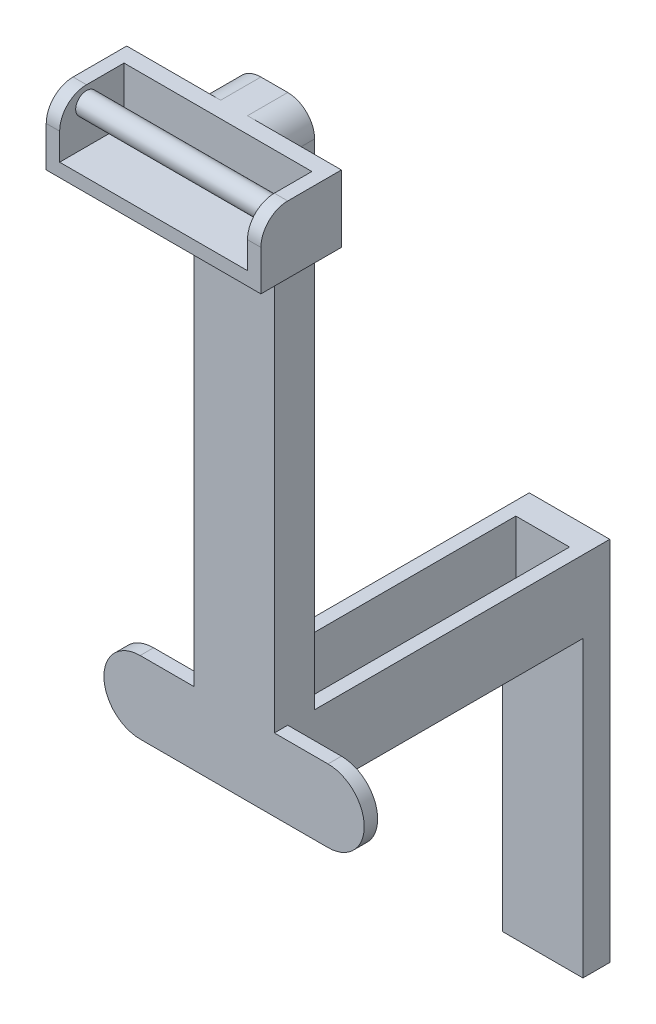
SolidWorks part; units mm, degrees
ref_plane "Front Plane" through (0, 0, 0) normal (0, 0, 1) x (1, 0, 0)
ref_plane "Top Plane" through (0, 0, 0) normal (0, 1, 0) x (1, 0, 0)
ref_plane "Right Plane" through (0, 0, 0) normal (1, 0, 0) x (0, 0, -1)
sketch "Sketch1" plane through (0, 0, 0) normal (0, 0, 1) x (1, 0, 0)
  line L0 (50, 212.065) -> (-20, 212.065) construction
  line L1 (30, -62.835) -> (0, -62.835)
  line L2 (30, -62.835) -> (30, 419.765)
  line L3 (30, 419.765) -> (0, 419.765)
  line L4 (0, -62.835) -> (0, 419.765)
  line L5 (30, -62.835) -> (0, 419.765) construction
  line L6 (30, 419.765) -> (0, -62.835) construction
  line L7 (50, 198.565) -> (-20, 198.565)
  line L8 (50, 225.565) -> (-20, 225.565)
  arc A0 (50, 198.565) -> (50, 225.565) centre (50, 212.065) ccw
  arc A1 (-20, 225.565) -> (-20, 198.565) centre (-20, 212.065) ccw
  point P0 (15, 178.465)
  point P7 (15, 212.065)
  dimension "D1" = 482.6
  dimension "D2" = 27
  dimension "D3" = 30
  dimension "D4" = 33.6
  dimension "D5" = 70
  dimension "D6" = 0
extrude "Extrude1" add sketch "Sketch1" along normal blind 15 contours L8 L2 L3 L4 | L7 A0 L8 L2 | L2 L8 L4 L7 | L8 A1 L7 L4 | L2 L7 L4 L1 region at (15, 67.865, 0) region at (15, 212.065, 0) region at (45.4498, 212.065, 0) region at (-15.4498, 212.065, 0) region at (15, 322.665, 0)
fillet "Fillet1" radius 10 4 edges at (30, -62.835, 7.5) (0, -62.835, 7.5) (0, 419.765, 7.5) (30, 419.765, 7.5)
sketch "Sketch2" plane through (0, 0, 0) normal (0, 0, -1) x (-1, 0, 0)
  line L0 (-50, 225.565) -> (-30, 225.565) construction
  line L1 (-50, 198.565) -> (-30, 198.565) construction
  line L2 (0, 198.565) -> (20, 198.565) construction
  line L3 (0, 225.565) -> (20, 225.565) construction
  line L4 (-50, 225.565) -> (-30, 225.565)
  line L5 (-50, 198.565) -> (-30, 198.565)
  line L6 (0, 198.565) -> (20, 198.565)
  line L7 (0, 225.565) -> (20, 225.565)
  line L8 (-30, 225.565) -> (-30, 198.565)
  line L9 (0, 225.565) -> (0, 198.565)
  arc A0 (20, 198.565) -> (20, 225.565) centre (20, 212.065) ccw construction
  arc A1 (-50, 225.565) -> (-50, 198.565) centre (-50, 212.065) ccw construction
  arc A2 (20, 198.565) -> (20, 225.565) centre (20, 212.065) ccw
  arc A3 (-50, 225.565) -> (-50, 198.565) centre (-50, 212.065) ccw
extrude "Extrude2" cut sketch "Sketch2" against normal blind 10
sketch "Sketch3" plane through (0, 0, 15) normal (0, 0, 1) x (1, 0, 0)
  line L0 (30, 407.265) -> (0, 407.265) construction
  line L1 (-25, 394.765) -> (55, 394.765)
  line L2 (-25, 394.765) -> (-25, 419.765)
  line L3 (-25, 419.765) -> (55, 419.765)
  line L4 (55, 394.765) -> (55, 419.765)
  line L5 (-25, 394.765) -> (55, 419.765) construction
  line L6 (-25, 419.765) -> (55, 394.765) construction
  line L7 (30, 225.565) -> (30, 409.765) construction
  line L8 (0, 225.565) -> (0, 409.765) construction
  line L9 (15, 407.265) -> (15, 419.765) construction
  line L10 (20, 419.765) -> (10, 419.765) construction
  point P0 (15, 407.265)
  dimension "D1" = 80
  dimension "D2" = 0
  dimension "D3" = 25
  dimension "D4" = 0
extrude "Extrude3" add sketch "Sketch3" along normal blind 30
sketch "Sketch5" plane through (0, 0, 45) normal (0, 0, 1) x (1, 0, 0)
  line L0 (55, 419.765) -> (-25, 419.765) construction
  line L1 (-20, 419.765) -> (50, 419.765)
  line L2 (-20, 419.765) -> (-20, 399.765)
  line L3 (-20, 399.765) -> (50, 399.765)
  line L4 (50, 419.765) -> (50, 399.765)
  line L5 (-25, 419.765) -> (-25, 394.765) construction
  line L6 (55, 394.765) -> (55, 419.765) construction
  line L7 (-25, 394.765) -> (55, 394.765) construction
  dimension "D1" = 5
  dimension "D2" = 5
  dimension "D3" = 5
extrude "Extrude4" cut sketch "Sketch5" against normal blind 24
fillet "Fillet2" radius 10 2 edges at (-22.5, 419.765, 45) (52.5, 419.765, 45)
sketch "Sketch6" plane through (50, 0, 0) normal (-1, 0, 0) x (0, 0, 1)
  circle A0 centre (35, 413.8477) radius 4.0292
extrude "Extrude5" add sketch "Sketch6" along normal up to next
sketch "Sketch7" plane through (0, 0, 0) normal (0, 0, -1) x (-1, 0, 0)
  line L0 (0, 198.565) -> (-30, 198.565)
  line L1 (-30, 198.565) -> (-30, -64.8073)
  line L2 (-30, -64.8073) -> (0, -64.8073)
  line L3 (0, -64.8073) -> (0, 198.565)
extrude "Extrude6" cut sketch "Sketch7" against normal through all
sketch "Sketch8" plane through (0, 0, 0) normal (0, 0, -1) x (-1, 0, 0)
  line L0 (-30, 198.565) -> (0, 198.565)
  line L1 (0, 198.565) -> (0, 225.565)
  line L2 (0, 225.565) -> (-5, 225.565)
  line L3 (-5, 225.565) -> (-5, 203.565)
  line L4 (-5, 203.565) -> (-25, 203.565)
  line L5 (-25, 203.565) -> (-25, 225.565)
  line L6 (-25, 225.565) -> (-30, 225.565)
  line L7 (-30, 198.565) -> (-30, 225.565) construction
  line L8 (-30, 198.565) -> (-30, 409.765) construction
  line L9 (-30, 225.565) -> (-30, 198.565)
  dimension "D1" = 5
  dimension "D2" = 5
  dimension "D3" = 5
extrude "Extrude7" add sketch "Sketch8" along normal blind 100
sketch "Sketch9" plane through (0, 0, -100) normal (0, 0, -1) x (-1, 0, 0)
  line L1 (-30, 225.565) -> (0, 225.565)
  line L2 (-30, 225.565) -> (-30, 88.9838)
  line L3 (-30, 88.9838) -> (0, 88.9838)
  line L4 (0, 225.565) -> (0, 88.9838)
extrude "Extrude8" add sketch "Sketch9" along normal blind 10
